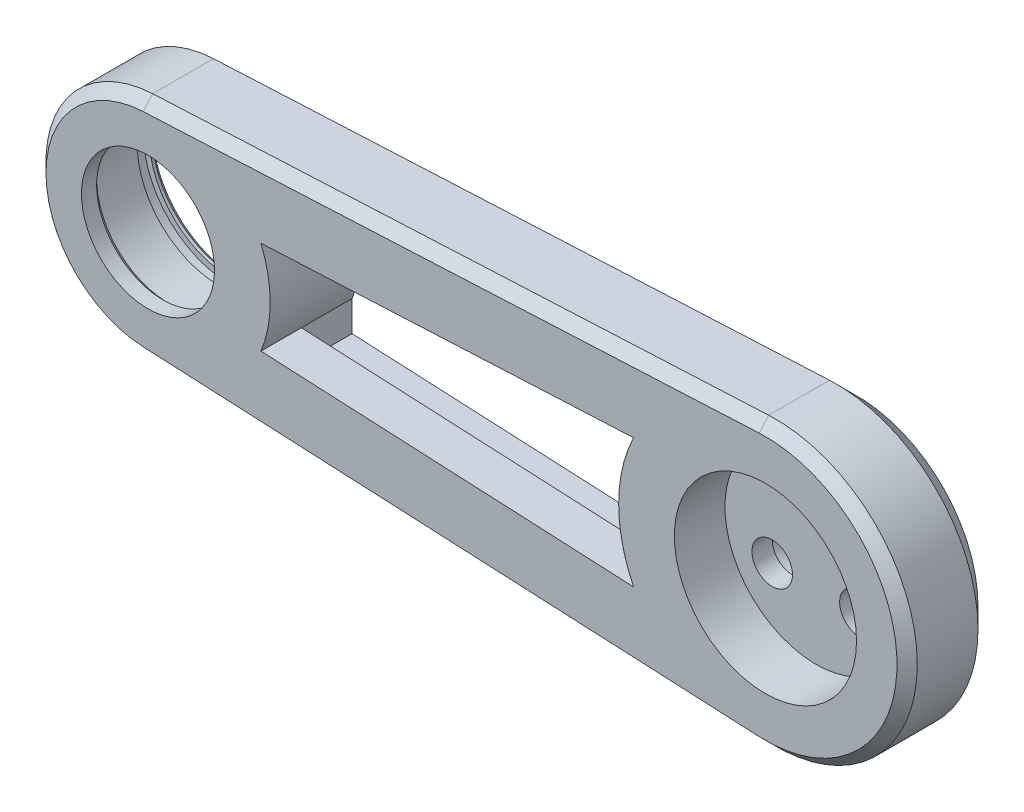
SolidWorks part; units mm, degrees
material "PEI"
ref_plane "前视基准面" through (0, 0, 0) normal (0, 0, 1) x (1, 0, 0)
ref_plane "上视基准面" through (0, 0, 0) normal (0, 1, 0) x (1, 0, 0)
ref_plane "右视基准面" through (0, 0, 0) normal (1, 0, 0) x (0, 0, -1)
other "Configuration Table"
sketch "草图2" plane through (0, 0, 0) normal (0, 0, 1) x (1, 0, 0)
  line L0 (0, 0) -> (61, 0) construction
  line L1 (-0.5311, 11.0623) -> (60.3287, 13.9839)
  line L2 (-0.5311, -11.0623) -> (60.3287, -13.9839)
  circle A0 centre (61, 0) radius 9
  circle A1 centre (61, 0) radius 14
  circle A2 centre (0, 0) radius 8.075
  circle A3 centre (0, 0) radius 11.075
  dimension "D1" = 18
  dimension "D2" = 28
  dimension "D4" = 16.15
  dimension "D3" = 61
  dimension "D5" = 3
extrude "凸台-拉伸1" add sketch "草图2" against normal blind 7 contours A2 A3 | A3 L0 A1 L1 | L0 A3 L2 A1 | A1 A0 region at (7.425, -7.79, 0) region at (29.7487, 6.7125, 0) region at (29.7487, -6.7125, 0) region at (51.1526, 9.386, 0)
sketch "草图3" plane through (0, 0, -7) normal (0, 0, -1) x (-1, 0, 0)
  line L2 (-60.3287, -13.9839) -> (0.5311, -11.0623)
  line L3 (0.5311, 11.0623) -> (-60.3287, 13.9839)
  line L4 (-60.3287, -13.9839) -> (0.5311, -11.0623)
  line L5 (0.5311, 11.0623) -> (-60.3287, 13.9839)
  circle A0 centre (-61, 0) radius 9 construction
  circle A1 centre (-61, 0) radius 9
  arc A2 (0.5311, -11.0623) -> (0.5311, 11.0623) centre (0, 0) ccw
  arc A3 (-60.3287, 13.9839) -> (-60.3287, -13.9839) centre (-61, 0) ccw
  arc A4 (0.5311, -11.0623) -> (0.5311, 11.0623) centre (0, 0) ccw
  arc A5 (-60.3287, 13.9839) -> (-60.3287, -13.9839) centre (-61, 0) ccw
  circle A6 centre (0, 0) radius 8.075 construction
  circle A7 centre (0, 0) radius 8.075
  line M5 (-60.3287, -13.9839) -> (0.5311, -11.0623)
  arc M6 (0.5311, -11.0623) -> (0.5311, 11.0623) centre (0, 0) ccw
  line M7 (0.5311, 11.0623) -> (-60.3287, 13.9839)
  arc M8 (-60.3287, 13.9839) -> (-60.3287, -13.9839) centre (-61, 0) ccw
  circle M9 centre (0, 0) radius 8.075
  circle M10 centre (-61, 0) radius 9
  dimension "D1" = 0
extrude "凸台-拉伸2" add sketch "草图3" along normal blind 3 contours M10 | M8 M5 M6 M7 M9 M10 region at (33.5142, 0, -7) region at (61, 0, -7)
sketch "草图4" plane through (0, 0, 0) normal (0, 0, 1) x (1, 0, 0)
  circle A0 centre (0, 0) radius 8.075 construction
  circle A1 centre (0, 0) radius 8.075
  circle A2 centre (0, 0) radius 6.575
  dimension "D1" = 1.5
extrude "凸台-拉伸3" add sketch "草图4" against normal blind 3
chamfer "倒角1" distance 0.5 angle 45 4 edges at (70, 0, 0) (-8.075, 0, -10) (6.575, 0, -3) (6.575, 0, 0)
chamfer "倒角2" distance 2 angle 45 8 edges at (29.8988, -12.5231, -10) (-11.075, 0, -10) (75, 0, -10) (29.8988, 12.5231, -10) (29.8988, -12.5231, 0) (-11.075, 0, 0) (75, 0, 0) (29.8988, 12.5231, 0)
sketch "草图5" plane through (0, 0, -10) normal (0, 0, -1) x (-1, 0, 0)
  line L0 (-85.5329, 0) -> (49.23, 0) construction
  line L1 (-61, 18.9424) -> (-61, -22.3961) construction
  circle A0 centre (-61, 0) radius 5 construction
  circle A1 centre (-61, 0) radius 9
  circle A2 centre (-61, 0) radius 9
  circle A3 centre (-61, 5) radius 2
  circle A7 centre (-56.6699, -2.5) radius 2
  circle A8 centre (-65.3301, -2.5) radius 2
  dimension "D2" = 10
  dimension "D3" = 4
  dimension "D1" = 0
extrude "切除-拉伸1" cut sketch "草图5" against normal up to surface (3 mm away) contours A3 | A8 | A7 region at (61, 5, -10) region at (56.6699, -2.5, -10) region at (65.3301, -2.5, -10) up to face at (70, 0, -7)
sketch "草图6" plane through (0, 0, 0) normal (0, 0, 1) x (1, 0, 0)
  line L0 (60.6643, 6.9919) -> (-0.1954, 4.0703)
  line L1 (-0.1954, -4.0703) -> (60.6643, -6.9919)
  line L2 (-0.4352, -9.0646) -> (60.4246, -11.9862)
  line L3 (60.4246, 11.9862) -> (-0.4352, 9.0646)
  line L4 (-0.4352, -9.0646) -> (60.4246, -11.9862)
  line L5 (60.4246, 11.9862) -> (-0.4352, 9.0646)
  circle A0 centre (0, 0) radius 7.075 construction
  circle A1 centre (0, 0) radius 7.075
  arc A2 (-0.4352, 9.0646) -> (-0.4352, -9.0646) centre (0, 0) ccw
  arc A3 (60.4246, -11.9862) -> (60.4246, 11.9862) centre (61, 0) ccw
  arc A4 (-0.4352, 9.0646) -> (-0.4352, -9.0646) centre (0, 0) ccw
  arc A5 (60.4246, -11.9862) -> (60.4246, 11.9862) centre (61, 0) ccw
  circle A6 centre (61, 0) radius 9.5 construction
  circle A7 centre (61, 0) radius 9.5
  arc A9 (-0.1954, 4.0703) -> (-0.1954, -4.0703) centre (0, 0) ccw
  arc A10 (60.6643, -6.9919) -> (60.6643, 6.9919) centre (61, 0) ccw
  circle A12 centre (0, 0) radius 12.075
  circle A13 centre (61, 0) radius 14.5
  dimension "D1" = 0
  dimension "D2" = 5
  dimension "D3" = 5
extrude "切除-拉伸2" cut sketch "草图6" against normal up to surface (10 mm away) contours A13 L0 A12 L1 region at (30.2812, 0, 0) up to face at (59, 5, -10)
sketch "草图7" plane through (0, 0, -10) normal (0, 0, -1) x (-1, 0, 0)
  line L0 (-11.1581, -4.6154) -> (-47.9805, -6.383) construction
  line L1 (-47.9805, 6.383) -> (-11.1581, 4.6154) construction
  line L2 (-11.1581, -4.6154) -> (-47.9805, -6.383)
  line L3 (-47.9805, 6.383) -> (-11.1581, 4.6154)
  line L4 (-47.9805, 9.3865) -> (-11.1581, 7.6188)
  line L5 (-47.9805, -9.3865) -> (-11.1581, -7.6188)
  line L6 (-47.9805, -9.3865) -> (-47.9805, -6.383)
  line L7 (-11.1581, -7.6188) -> (-11.1581, -4.6154)
  line L8 (-11.1581, 7.6188) -> (-11.1581, 4.6154)
  line L9 (-47.9805, 9.3865) -> (-47.9805, 6.383)
  line M5 (-47.9805, 6.383) -> (-11.1581, 4.6154)
  line M7 (-11.1581, -4.6154) -> (-47.9805, -6.383)
  dimension "D1" = 3
  dimension "D2" = 3
extrude "切除-拉伸3" cut sketch "草图7" against normal blind 5 contours L4 L9 L8 M5 | L5 L7 L6 M7 region at (29.5693, -7.0009, -10) region at (29.5693, 7.0009, -10)
sketch "草图8" plane through (0, 0, 0) normal (0, 1, 0) x (1, 0, 0)
  line L0 (8.075, 3) -> (-8.075, 3) construction
  line L1 (8.075, 3) -> (-8.075, 3)
  line L2 (0, 3) -> (0, 12.4647) construction
  line L4 (8.075, 8) -> (8.65, 8)
  line L5 (8.65, 8) -> (8.65, 9.2)
  line L6 (8.65, 9.2) -> (8.075, 9.2)
  line L7 (8.075, 9.2) -> (8.075, 8)
  dimension "D1" = 1.2
  dimension "D2" = 5
  dimension "D3" = 8.075
  dimension "D4" = 8.65
revolve "切除-旋转1" cut sketch "草图8" angle 360 about L2 region at (8.3625, 0, -8.6)
sketch "草图9" plane through (0, 0, 0) normal (0, 0, 1) x (1, 0, 0)
  line L0 (60.3287, -13.9839) -> (-0.5311, -11.0623) construction
  line L1 (-0.5311, 11.0623) -> (60.3287, 13.9839) construction
  line L2 (60.3287, -13.9839) -> (-0.5311, -11.0623)
  line L3 (-0.5311, 11.0623) -> (60.3287, 13.9839)
  arc A0 (60.3287, -13.9839) -> (60.3287, 13.9839) centre (61, 0) ccw construction
  arc A1 (-0.5311, 11.0623) -> (-0.5311, -11.0623) centre (0, 0) ccw construction
  arc A2 (60.3287, -13.9839) -> (60.3287, 13.9839) centre (61, 0) ccw
  arc A3 (-0.5311, 11.0623) -> (-0.5311, -11.0623) centre (0, 0) ccw
extrude "切除-拉伸4" cut sketch "草图9" against normal blind 1
sketch "草图10" plane through (0, 0, -7) normal (0, 0, 1) x (1, 0, 0)
  circle A0 centre (61, 5) radius 2 construction
  circle A1 centre (61, 0) radius 9
  circle A2 centre (61, 0) radius 9
  circle A3 centre (61, 5) radius 2
  circle A4 centre (56.6699, -2.5) radius 2 construction
  circle A5 centre (56.6699, -2.5) radius 2
  circle A6 centre (65.3301, -2.5) radius 2 construction
  circle A7 centre (65.3301, -2.5) radius 2
  circle M3 centre (61, 5) radius 2
  circle M4 centre (65.3301, -2.5) radius 2
  circle M5 centre (56.6699, -2.5) radius 2
  circle M6 centre (61, 0) radius 9
  dimension "D1" = 0
extrude "凸台-拉伸4" add sketch "草图10" along normal blind 1 contours M6 M4 M5 M3 region at (61, 0, -7)
sketch "草图11" plane through (0, 0, -10) normal (0, 0, -1) x (-1, 0, 0)
  circle A0 centre (-56.6699, -2.5) radius 2 construction
  circle A1 centre (-65.3301, -2.5) radius 2 construction
  circle A2 centre (-61, 5) radius 2 construction
  circle A3 centre (-56.6699, -2.5) radius 2
  circle A4 centre (-65.3301, -2.5) radius 2
  circle A5 centre (-61, 5) radius 2
  circle A6 centre (-61, 5) radius 2.85
  circle A7 centre (-65.3301, -2.5) radius 2.85
  circle A8 centre (-56.6699, -2.5) radius 2.85
  dimension "D1" = 5.7
  dimension "D2" = 5.7
  dimension "D3" = 5.7
extrude "切除-拉伸5" cut sketch "草图11" against normal blind 2
equation "\"D3@草图2\"= \"从动杆_前_长度\""
equation "\"从动杆_前_长度\"= 61"
